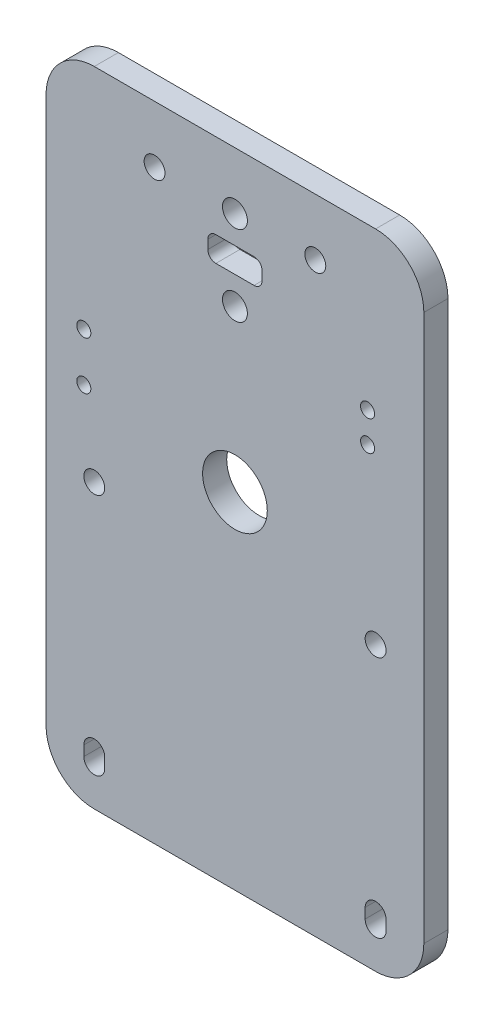
SolidWorks part; units mm, degrees
material "Polycarbonate (PC)"
ref_plane "Спереди" through (0, 0, 0) normal (0, 0, 1) x (1, 0, 0)
ref_plane "Сверху" through (0, 0, 0) normal (0, 1, 0) x (1, 0, 0)
ref_plane "Справа" through (0, 0, 0) normal (1, 0, 0) x (0, 0, -1)
sketch "Model" plane through (0, 0, 0) normal (0, 0, 1) x (1, 0, 0)
  line L5 (0, 170.1561) -> (0, 0) construction
  line L24 (-35, 37.2847) -> (-35, 78.8619) construction
  line L25 (-31.4983, 12.5) -> (-38.4, 12.5) construction
  line L26 (-31.4983, 10) -> (-38.4, 10) construction
  line L27 (-35, 12.5) -> (-35, 10) construction
  line L28 (-32.4, 12.5) -> (-32.4, 10)
  line L29 (-37.6, 12.5) -> (-37.6, 10)
  line L40 (31.4983, 10) -> (38.4, 10) construction
  line L41 (31.4983, 12.5) -> (38.4, 12.5) construction
  line L42 (35, 37.2847) -> (35, 78.8619) construction
  line L43 (35, 12.5) -> (35, 10) construction
  line L44 (32.4, 12.5) -> (32.4, 10)
  line L45 (37.6, 12.5) -> (37.6, 10)
  line L47 (-26.0102, 145.8) -> (26.0946, 145.8) construction
  line L50 (-20, 133.6948) -> (-20, 127.8457) construction
  line L51 (-38.85, 70.45) -> (-29.8907, 70.45) construction
  line L53 (-16.3166, 125.8) -> (17.7871, 125.8) construction
  line L58 (38.85, 70.45) -> (29.8907, 70.45) construction
  line L4875 (-35, 160) -> (35, 160)
  line L4882 (47, 148) -> (47, 12)
  line L4889 (35, 0) -> (-35, 0)
  line L4896 (-47, 12) -> (-47, 148)
  line L6648 (-6.75, 138.9) -> (6.75, 138.9)
  line L6649 (6.75, 138.9) -> (6.75, 132.7)
  line L6650 (6.75, 132.7) -> (-6.75, 132.7)
  line L6651 (-6.75, 132.7) -> (-6.75, 138.9)
  arc A0 (-47, 12) -> (-35, 0) centre (-35, 12) ccw
  arc A1 (35, 0) -> (47, 12) centre (35, 12) ccw
  arc A2 (47, 148) -> (35, 160) centre (35, 148) ccw
  arc A3 (-35, 160) -> (-47, 148) centre (-35, 148) ccw
  arc A13 (-32.4, 12.5) -> (-37.6, 12.5) centre (-35, 12.5) ccw
  arc A14 (-37.6, 10) -> (-32.4, 10) centre (-35, 10) ccw
  arc A19 (32.4, 12.5) -> (37.6, 12.5) centre (35, 12.5) cw
  arc A20 (37.6, 10) -> (32.4, 10) centre (35, 10) cw
  circle A29 centre (0, 145.8) radius 3.1
  circle A30 centre (-20, 145.8) radius 2.6
  circle A31 centre (20, 145.8) radius 2.6
  circle A32 centre (-35, 70.45) radius 2.6
  circle A33 centre (0, 125.8) radius 3.1
  circle A36 centre (35, 70.45) radius 2.6
  point P0 (-6.75, 135.8)
  point P17 (0, 0)
  point P77 (-35, 11.25)
  point P114 (35, 11.25)
  dimension "D5" = 5.2
  dimension "D8" = 13.5
  dimension "D35" = 6.2
  dimension "D13" = 12
  dimension "D3" = 160
  dimension "D6" = 20
  dimension "D7" = 20
  dimension "D9" = 70
  dimension "D10" = 60.45
  dimension "D11" = 24.2
  dimension "D12" = 94
  dimension "D16" = 2.5
  dimension "D17" = 10
  dimension "D18" = 5.2
  dimension "D25" = 14.2
  dimension "D34" = 20
  dimension "D42" = 6.2
extrude "Base" add sketch "Model" along normal blind 6 contours L4875 A3 L4896 A0 L4889 A1 L4882 A2 L45 A20 L44 A19 region at (0, 79.6086, 0)
sketch "Эскиз1" plane through (0, 0, 0) normal (0, 0, -1) x (-1, 0, 0)
  line L0 (35, 160) -> (-35, 160) construction
  line L1 (0, 160) -> (0, 146.8198) construction
  circle A0 centre (0, 85.8) radius 8.05
  dimension "D2" = 16.1
  dimension "D1" = 74.2
extrude "BearingHole" cut sketch "Эскиз1" against normal blind 10
sketch "Sketch1" plane through (0, 0, 6) normal (0, 0, 1) x (1, 0, 0)
  line L0 (-35, 160) -> (35, 160) construction
  line L1 (47, 148) -> (47, 12) construction
  circle A0 centre (33, 120) radius 1.75
  circle A1 centre (33, 112.5) radius 1.75
  dimension "D1" = 3.5
  dimension "D3" = 7.5
  dimension "D4" = 40
  dimension "D5" = 14
extrude "SensorMount" cut sketch "Sketch1" against normal blind 10
sketch "Sketch3" plane through (0, 0, 0) normal (0, 0, -1) x (-1, 0, 0)
  line L1 (47, 12) -> (47, 148) construction
  line L3 (-35, 0) -> (35, 0) construction
  circle A0 centre (37.6, 90.0886) radius 1.75
  circle A1 centre (37.6, 102.0886) radius 1.75
  dimension "D3" = 3.5
  dimension "D4" = 90.0886
  dimension "D1" = 12
  dimension "D2" = 9.4
extrude "CableMount" cut sketch "Sketch3" against normal blind 10
fillet "FilletCableSlot" radius 2 4 edges at (6.75, 138.9, 3) (-6.75, 138.9, 3) (-6.75, 132.7, 3) (6.75, 132.7, 3)
ref_plane "Plane1" through (0, 40.225, 0) normal (0, -1, 0) x (-1, 0, 0)
